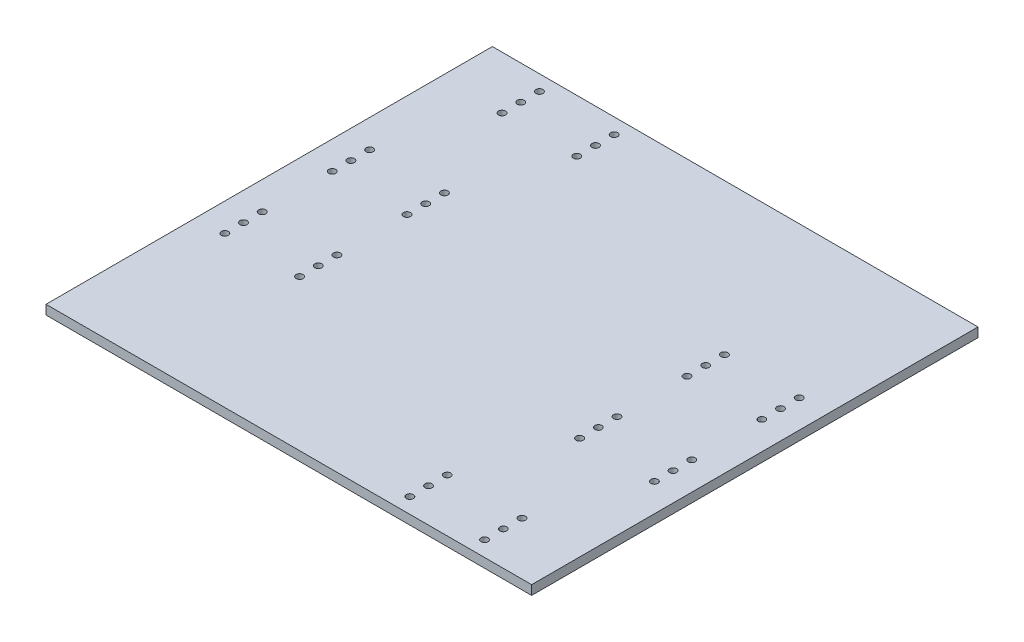
SolidWorks part; units mm, degrees
ref_plane "Alzado" through (0, 0, 0) normal (0, 0, 1) x (1, 0, 0)
ref_plane "Planta" through (0, 0, 0) normal (0, 1, 0) x (1, 0, 0)
ref_plane "Vista lateral" through (0, 0, 0) normal (1, 0, 0) x (0, 0, -1)
sketch "Croquis1" plane through (0, 0, 0) normal (0, 1, 0) x (1, 0, 0)
  line L1 (165, -151.655) -> (-165, -151.655)
  line L2 (165, -151.655) -> (165, 151.655)
  line L3 (165, 151.655) -> (-165, 151.655)
  line L4 (-165, -151.655) -> (-165, 151.655)
  line L5 (165, -151.655) -> (-165, 151.655) construction
  line L6 (165, 151.655) -> (-165, -151.655) construction
  point P0 (0, 0)
  dimension "D1" = 330
  dimension "D2" = 303.31
extrude "Saliente-Extruir2" add sketch "Croquis1" along normal blind 6.35
sketch "Croquis2" plane through (0, 6.35, 0) normal (0, 1, 0) x (1, 0, 0)
  line L0 (-165, 129.3909) -> (165, 129.3909) construction
  line L3 (-165, 151.655) -> (-165, -151.655) construction
  line L4 (165, -151.655) -> (165, 151.655) construction
sketch "Croquis3" plane through (0, 6.35, 0) normal (0, 1, 0) x (1, 0, 0)
  line L0 (-165, -151.655) -> (165, -151.655) construction
  line L1 (-165, 151.655) -> (-135.28, 151.655)
  line L2 (-165, 151.655) -> (-165, -151.655)
  line L3 (-165, -151.655) -> (-135.28, -151.655)
  line L4 (-135.28, 151.655) -> (-135.28, -151.655)
  line L5 (-165, -118.245) -> (165, -118.245) construction
  line L6 (165, -151.655) -> (165, 151.655) construction
  line L7 (-122.58, -147.8926) -> (-122.58, -88.5974) construction
  line L8 (-97.18, -151.655) -> (-97.18, -77.7371) construction
  line L9 (0, 151.655) -> (0, -151.655) construction
  line L10 (165, 151.655) -> (-165, 151.655) construction
  line L11 (-165, 0) -> (165, 0) construction
  circle A0 centre (-122.58, -118.245) radius 3.9687
  circle A1 centre (-122.58, -105.545) radius 3.9687
  circle A2 centre (-122.58, -130.945) radius 3.9687
  circle A3 centre (-71.78, -130.945) radius 3.9687
  circle A4 centre (-71.78, -118.245) radius 3.9687
  circle A5 centre (-71.78, -105.545) radius 3.9687
  circle A24 centre (122.58, 118.245) radius 3.9687
  circle A25 centre (122.58, 105.545) radius 3.9687
  circle A26 centre (122.58, 130.945) radius 3.9687
  circle A27 centre (71.78, 130.945) radius 3.9687
  circle A28 centre (71.78, 118.245) radius 3.9687
  circle A29 centre (71.78, 105.545) radius 3.9687
  point P16 (-122.58, -118.245)
  point P59 (122.58, 118.245)
  dimension "D3" = 12.7
  dimension "D4" = 7.9375
  dimension "D5" = 12.7
  dimension "D6" = 12.7
  dimension "D1" = 29.72
  dimension "D2" = 33.41
  dimension "D7" = 25.4
sketch "Croquis4" plane through (0, 6.35, 0) normal (0, 1, 0) x (1, 0, 0)
  line L0 (0, 151.655) -> (0, -151.655) construction
  line L1 (165, 151.655) -> (-165, 151.655) construction
  line L2 (-165, -151.655) -> (165, -151.655) construction
  line L3 (-158.65, 151.655) -> (-158.65, -151.655) construction
  line L4 (-165, 151.655) -> (-165, -151.655) construction
  line L5 (158.65, 151.655) -> (158.65, -151.655) construction
  line L6 (0, -159.495) -> (270.56, -159.495) construction
  line L7 (135.28, -159.495) -> (135.28, -97.519) construction
  line L8 (122.58, -159.495) -> (122.58, -97.519) construction
  line L9 (122.58, -128.507) -> (158.65, -128.507) construction
  line L10 (97.18, -159.495) -> (97.18, -97.519) construction
  line L11 (82.45, -36.499) -> (158.65, -36.499) construction
  line L12 (135.28, -97.519) -> (59.08, -97.519) construction
  line L13 (135.28, -97.519) -> (135.28, -159.495) construction
  line L14 (135.28, -159.495) -> (59.08, -159.495) construction
  line L15 (59.08, -97.519) -> (59.08, -159.495) construction
  line L16 (158.65, -5.509) -> (82.45, -5.509) construction
  line L17 (158.65, -5.509) -> (158.65, -67.489) construction
  line L18 (158.65, -67.489) -> (82.45, -67.489) construction
  line L19 (82.45, -5.509) -> (82.45, -67.489) construction
  line L20 (120.55, -5.509) -> (120.55, -67.489) construction
  line L21 (95.15, -5.509) -> (95.15, -67.489) construction
  line L22 (165, 0) -> (-165, 0) construction
  line L23 (165, -151.655) -> (165, 151.655) construction
  circle A1 centre (122.58, -128.507) radius 2.3813
  circle A2 centre (122.58, -115.807) radius 2.3813
  circle A3 centre (122.58, -141.207) radius 2.3813
  circle A4 centre (71.78, -141.207) radius 2.3813
  circle A5 centre (71.78, -128.507) radius 2.3813
  circle A6 centre (71.78, -115.807) radius 2.3813
  circle A7 centre (95.15, -36.499) radius 2.3813
  circle A8 centre (95.15, -23.799) radius 2.3813
  circle A9 centre (95.15, -49.199) radius 2.3813
  circle A10 centre (145.95, -49.199) radius 2.3813
  circle A11 centre (145.95, -36.499) radius 2.3813
  circle A12 centre (145.95, -23.799) radius 2.3813
  circle A19 centre (145.95, 49.199) radius 2.3813
  circle A20 centre (95.15, 49.199) radius 2.3813
  circle A21 centre (145.95, 36.499) radius 2.3813
  circle A22 centre (95.15, 36.499) radius 2.3813
  circle A23 centre (145.95, 23.799) radius 2.3813
  circle A24 centre (95.15, 23.799) radius 2.3813
  circle A31 centre (-95.15, -49.199) radius 2.3813
  circle A32 centre (-145.95, -49.199) radius 2.3813
  circle A33 centre (-145.95, -36.499) radius 2.3813
  circle A34 centre (-95.15, -36.499) radius 2.3813
  circle A35 centre (-95.15, -23.799) radius 2.3813
  circle A36 centre (-145.95, -23.799) radius 2.3813
  circle A37 centre (-145.95, 49.199) radius 2.3813
  circle A38 centre (-145.95, 36.499) radius 2.3813
  circle A39 centre (-145.95, 23.799) radius 2.3813
  circle A40 centre (-95.15, 23.799) radius 2.3813
  circle A41 centre (-95.15, 36.499) radius 2.3813
  circle A42 centre (-95.15, 49.199) radius 2.3813
  circle A43 centre (-122.58, 115.807) radius 2.3813
  circle A44 centre (-122.58, 128.507) radius 2.3813
  circle A45 centre (-122.58, 141.207) radius 2.3813
  circle A46 centre (-71.78, 115.807) radius 2.3813
  circle A47 centre (-71.78, 128.507) radius 2.3813
  circle A48 centre (-71.78, 141.207) radius 2.3813
  dimension "D7" = 4.7625
  dimension "D8" = 12.7
  dimension "D10" = 0
  dimension "D15" = 4.7625
  dimension "D16" = 12.7
  dimension "D18" = 4.7625
  dimension "D1" = 6.35
  dimension "D2" = 7.84
  dimension "D3" = 23.37
  dimension "D4" = 12.7
  dimension "D5" = 61.976
  dimension "D6" = 0
  dimension "D9" = 25.4
  dimension "D11" = 76.2
  dimension "D12" = 61.98
  dimension "D13" = 76.2
  dimension "D14" = 12.7
  dimension "D17" = 30.03
extrude "Cortar-Extruir1" cut sketch "Croquis4" against normal blind 10
